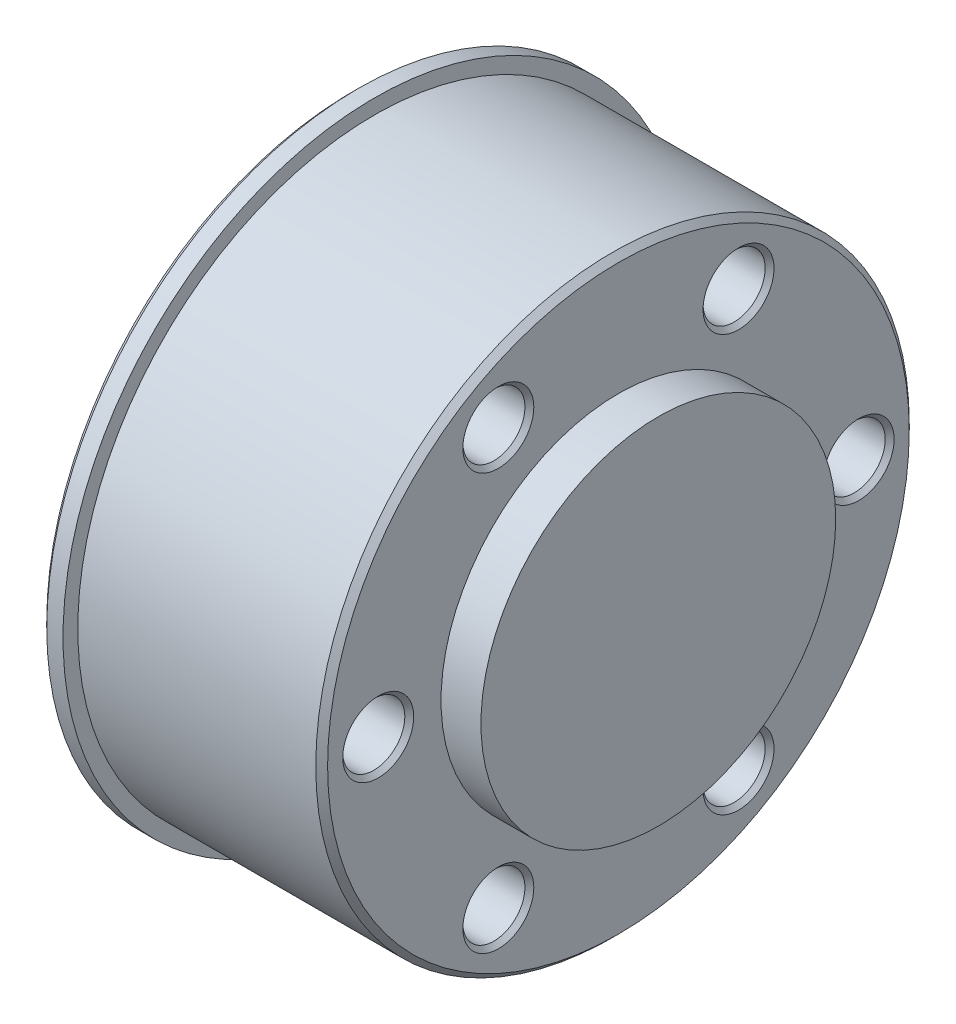
SolidWorks part; units mm, degrees
ref_plane "Front Plane" through (0, 0, 0) normal (0, 0, 1) x (1, 0, 0)
ref_plane "Top Plane" through (0, 0, 0) normal (0, 1, 0) x (1, 0, 0)
ref_plane "Right Plane" through (0, 0, 0) normal (1, 0, 0) x (0, 0, -1)
sketch "Sketch2" plane through (0, 0, 0) normal (0, 1, 0) x (1, 0, 0)
  line L0 (0, 0) -> (0, 12)
  line L1 (0, 12) -> (-2.7, 12)
  line L2 (-2.7, 12) -> (-2.7, 20.075)
  line L3 (-2.7, 20.075) -> (-19.2, 20.075)
  line L4 (-19.2, 20.075) -> (-19.2, 21.075)
  line L5 (-19.2, 21.075) -> (-20.7, 21.075)
  line L6 (-20.7, 21.075) -> (-20.7, 17.7278)
  line L7 (0, 0) -> (-41.2311, 0) construction
  line L11 (-20.7, 14.575) -> (-20.7, 8.1)
  line L12 (-20.7, 8.1) -> (-15.7, 8.1)
  line L13 (-15.7, 8.1) -> (-15.7, 6)
  line L14 (-15.7, 6) -> (-13.7, 6)
  line L15 (-13.7, 6) -> (-13.7, 0)
  line L16 (-13.7, 0) -> (0, 0)
  line L17 (-20.7, 17.7278) -> (-20.7, 14.575)
  dimension "D1" = 12
  dimension "D2" = 2.7
  dimension "D3" = 8.075
  dimension "D4" = 16.5
  dimension "D5" = 1
  dimension "D6" = 1.5
  dimension "D8" = 8.1
  dimension "D9" = 6
  dimension "D10" = 5
  dimension "D13" = 2
revolve "Revolve1" add sketch "Sketch2" angle 360 about L7
sketch "Sketch3" plane through (-20.7, 0, 0) normal (-1, 0, 0) x (0, 0, 1)
  circle A0 centre (0, 16) radius 1.625
  circle A1 centre (13.8564, 7.9047) radius 1.625
  circle A2 centre (13.7739, -8.1429) radius 1.625
  circle A3 centre (-0.165, -16.0953) radius 1.625
  circle A4 centre (-14.0214, -8) radius 1.625
  circle A5 centre (-13.9389, 8.0476) radius 1.625
  dimension "D1" = 3.25
  dimension "D3" = 16
  dimension "D2" = 6
extrude "Cut-Extrude1" cut sketch "Sketch3" against normal blind 12
sketch "Sketch4" plane through (-2.7, 0, 0) normal (1, 0, 0) x (0, 0, -1)
  line L0 (0, 0) -> (0, 20.075) construction
  line L1 (-8.125, 14.0729) -> (0, 0) construction
  circle A0 centre (-8.125, 14.0729) radius 2.1
  circle A1 centre (8.125, 14.0729) radius 2.1
  circle A2 centre (16.25, 0) radius 2.1
  circle A3 centre (8.125, -14.0729) radius 2.1
  circle A4 centre (-8.125, -14.0729) radius 2.1
  circle A5 centre (-16.25, 0) radius 2.1
  circle A6 centre (0, 0) radius 20.075 construction
  circle A7 centre (0, 0) radius 16.25 construction
  point P15 (0, 0)
  dimension "D1" = 4.2
  dimension "D2" = 30
  dimension "D3" = 6
  dimension "D4" = 16.25
extrude "Cut-Extrude2" cut sketch "Sketch4" against normal blind 10
sketch "Sketch5" plane through (-2.7, 0, 0) normal (1, 0, 0) x (0, 0, -1)
  line L1 (10.0375, 17.3855) -> (-10.0375, -17.3855) construction
  circle A0 centre (0, 0) radius 20.075 construction
  circle A1 centre (0, 0) radius 20.075 construction
chamfer "Chamfer1" distance 0.4 angle 45 1 edges at (-2.7, 0, -20.075)
chamfer "Chamfer2" distance 0.4 angle 45 1 edges at (-20.7, 0, -8.1)
chamfer "Chamfer3" distance 0.4 angle 45 6 edges at (-20.7, -16.0953, 1.46) (-20.7, -8, -12.3964) (-20.7, 8.0476, -12.3139) (-20.7, -8.1429, 15.3989) (-20.7, 7.9047, 15.4814) (-20.7, 16, 1.625)
chamfer "Chamfer4" distance 0.3 angle 45 6 edges at (-2.7, -14.0729, -10.225) (-2.7, 0, -18.35) (-2.7, 14.0729, -10.225) (-2.7, 14.0729, 6.025) (-2.7, -14.0729, 6.025) (-2.7, 0, 14.15)
chamfer "Chamfer5" distance 0.4 angle 45 1 edges at (-20.7, 0, -21.075)
